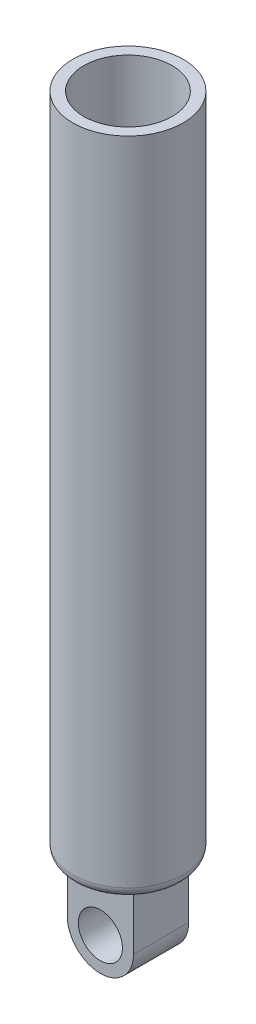
SolidWorks part; units mm, degrees
ref_plane "Front Plane" through (0, 0, 0) normal (0, 0, 1) x (1, 0, 0)
ref_plane "Top Plane" through (0, 0, 0) normal (0, 1, 0) x (1, 0, 0)
ref_plane "Right Plane" through (0, 0, 0) normal (1, 0, 0) x (0, 0, -1)
sketch "Sketch1" plane through (0, 0, 0) normal (0, 1, 0) x (1, 0, 0)
  circle A0 centre (0, 0) radius 25
  dimension "D1" = 50
extrude "Boss-Extrude1" add sketch "Sketch1" along normal blind 300
shell "Shell1" thickness 5
fillet "Fillet1" radius 5 1 edges at (0, 0, 25)
sketch "Sketch2" plane through (0, 0, 0) normal (0, -1, 0) x (1, 0, 0)
  line L1 (-15, -12.5) -> (15, -12.5)
  line L2 (-15, -12.5) -> (-15, 12.5)
  line L3 (-15, 12.5) -> (15, 12.5)
  line L4 (15, -12.5) -> (15, 12.5)
  line L5 (-15, -12.5) -> (15, 12.5) construction
  line L6 (-15, 12.5) -> (15, -12.5) construction
  point P0 (0, 0)
  dimension "D1" = 30
  dimension "D2" = 25
extrude "Boss-Extrude2" add sketch "Sketch2" along normal blind 40
sketch "Sketch3" plane through (0, 0, -12.5) normal (0, 0, -1) x (-1, 0, 0)
  line L0 (15, -40) -> (-15, -40) construction
  line L1 (15, -40) -> (15, 0) construction
  circle A0 centre (0, -25) radius 10
  point P4 (0, 0)
  dimension "D1" = 20
  dimension "D2" = 15
  dimension "D3" = 15
extrude "Cut-Extrude1" cut sketch "Sketch3" against normal blind 40
fillet "Fillet3" radius 15 2 edges at (-15, -40, 0) (15, -40, 0)
